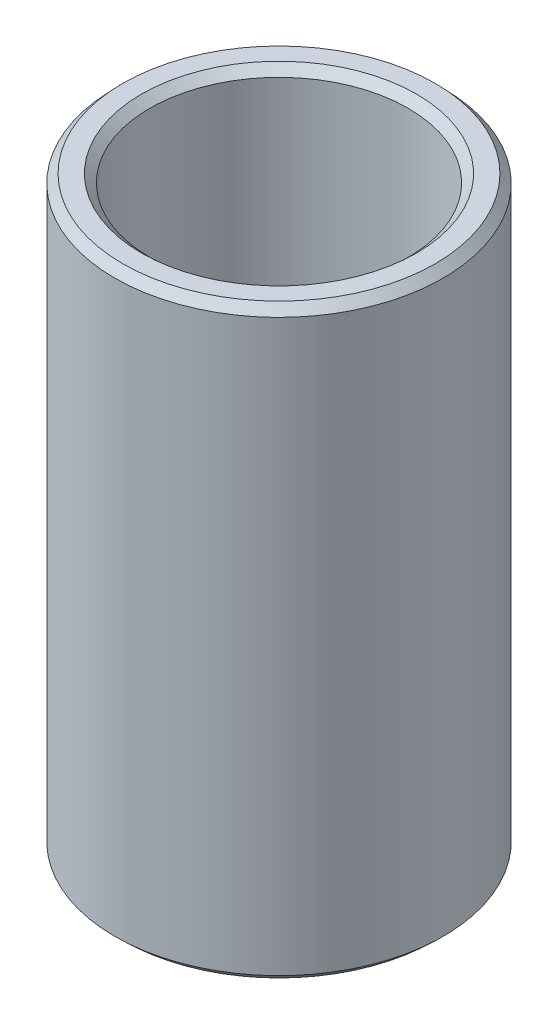
SolidWorks part; units mm, degrees
ref_plane "Front Plane" through (0, 0, 0) normal (0, 0, 1) x (1, 0, 0)
ref_plane "Top Plane" through (0, 0, 0) normal (0, 1, 0) x (1, 0, 0)
ref_plane "Right Plane" through (0, 0, 0) normal (1, 0, 0) x (0, 0, -1)
sketch "Sketch1" plane through (0, 0, 0) normal (0, 1, 0) x (1, 0, 0)
  circle A0 centre (0, 0) radius 57.5
  dimension "SLEEVE_OD" = 115
extrude "Boss-Extrude1" add sketch "Sketch1" along normal blind 205.373
sketch "Sketch2" plane through (0, 0, 0) normal (0, 1, 0) x (1, 0, 0)
  circle A0 centre (0, 0) radius 45.2237
  dimension "BORE_D" = 90.4475
extrude "Cut-Extrude1" cut sketch "Sketch2" along normal through all
chamfer "Chamfer1" distance 2.9597 angle 43.331 4 edges at (0, 205.373, 45.2237) (0, 0, 45.2237) (0, 0, 57.5) (0, 205.373, 57.5) first distance on face at (0, 205.373, 45.2237) first distance on face at (0, 0, 45.2237) first distance on face at (0, 205.373, 57.5)
